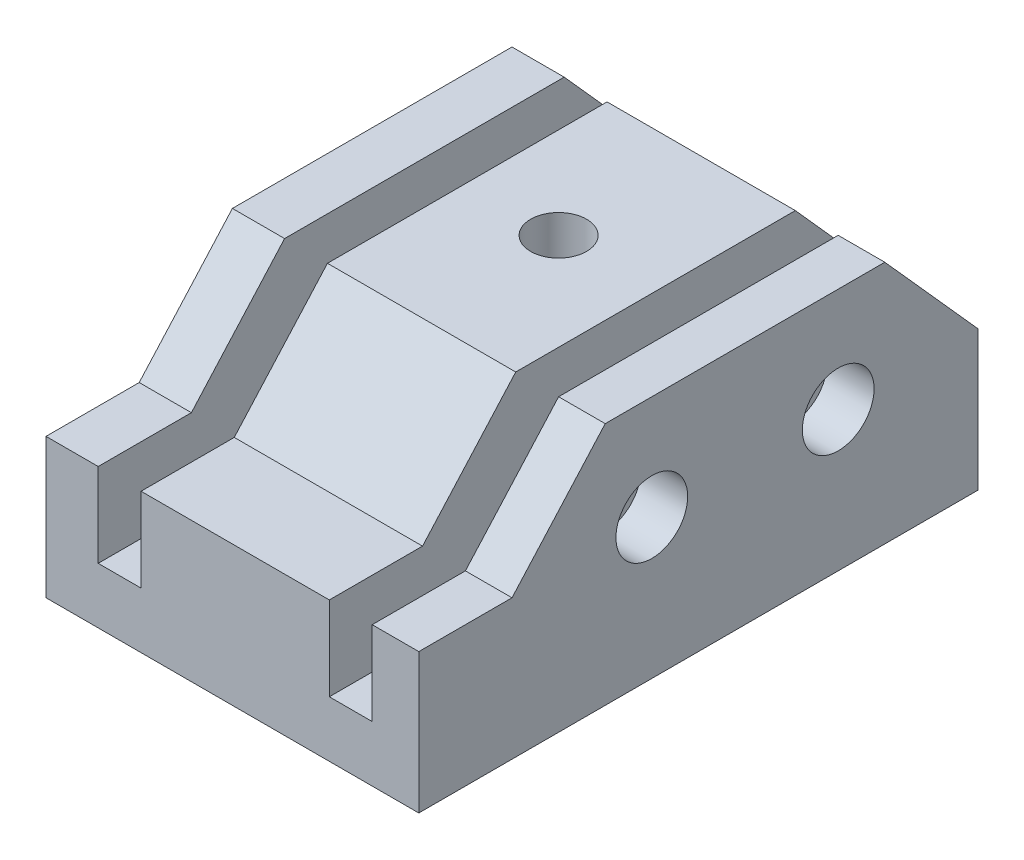
SolidWorks part; units mm, degrees
ref_plane "Front Plane" through (0, 0, 0) normal (0, 0, 1) x (1, 0, 0)
ref_plane "Top Plane" through (0, 0, 0) normal (0, 1, 0) x (1, 0, 0)
ref_plane "Right Plane" through (0, 0, 0) normal (1, 0, 0) x (0, 0, -1)
sketch "Sketch1" plane through (0, 0, 0) normal (1, 0, 0) x (0, 0, -1)
  line L1 (0, 0) -> (63.5, 0)
  line L2 (0, 0) -> (0, 6.35)
  line L3 (0, 6.35) -> (63.5, 6.35)
  line L4 (63.5, 0) -> (63.5, 6.35)
  dimension "D1" = 6.35
  dimension "D2" = 63.5
extrude "Boss-Extrude1" add sketch "Sketch1" against normal blind 50.8
sketch "Sketch2" plane through (0, 0, 0) normal (1, 0, 0) x (0, 0, -1)
  line L0 (0, 6.35) -> (0, 19.05)
  line L1 (0, 19.05) -> (12.7, 33.249)
  line L2 (12.7, 33.249) -> (50.8, 33.249)
  line L3 (50.8, 33.249) -> (63.5, 19.05)
  line L4 (63.5, 19.05) -> (63.5, 6.35)
  line L5 (63.5, 6.35) -> (0, 6.35)
  point P7 (31.75, 33.249)
  point P10 (31.75, 6.35)
  dimension "D1" = 38.1
  dimension "D2" = 12.7
  dimension "D3" = 12.7
  dimension "D4" = 19.05
  dimension "D5" = 19.05
extrude "Boss-Extrude2" add sketch "Sketch2" against normal blind 50.8
sketch "Sketch10" plane through (0, 0, -63.5) normal (0, 0, -1) x (-1, 0, 0)
  line L1 (50.8, 33.249) -> (0, 33.249) construction
  line L3 (6.35, 7.62) -> (6.35, 33.249)
  line L4 (6.35, 33.249) -> (12.192, 33.249)
  line L5 (12.192, 7.62) -> (12.192, 33.249)
  line L6 (6.35, 7.62) -> (12.192, 7.62)
  line L8 (50.8, 0) -> (0, 0) construction
  point P11 (12.192, 7.62)
  dimension "D1" = 7.62
  dimension "D2" = 5.842
  dimension "D3" = 6.35
extrude "Cut-Extrude1" cut sketch "Sketch10" against normal through all
pattern_linear "LPattern3" count 2 spacing 31.496 along (-1, 0, 0) of "Cut-Extrude1"
sketch "Sketch11" plane through (0, 0, 0) normal (1, 0, 0) x (0, 0, -1)
  circle A0 centre (19.05, 19.05) radius 4.8895
  circle A1 centre (19.05, 19.05) radius 7.9375 construction
  circle A2 centre (44.45, 19.05) radius 4.8895
  circle A3 centre (44.45, 19.05) radius 7.9375 construction
  dimension "D1" = 9.779
  dimension "D3" = 15.875
  dimension "D4" = 9.779
  dimension "D6" = 15.875
  dimension "D2" = 6.35
  dimension "D5" = 6.35
extrude "Cut-Extrude2" cut sketch "Sketch11" against normal through all
sketch "Sketch14" plane through (0, 33.249, 0) normal (0, 1, 0) x (1, 0, 0)
  line L3 (-37.846, 12.7) -> (-37.846, 50.8) construction
  point P0 (-25.4, 31.75)
  point P4 (-37.846, 31.75)
  dimension "D1" = 12.446
sketch "Sketch17" plane through (0, 40.0201, -44.7438) normal (0, 0.6667, -0.7454) x (-1, 0, 0)
  line L0 (12.192, -28.1343) -> (12.192, -9.0843) construction
  line L1 (37.846, -9.0843) -> (12.192, -9.0843) construction
  point P0 (25.019, -18.6093)
  point P4 (12.192, -18.6093)
  point P7 (25.019, -9.0843)
sketch "Sketch18" plane through (0, 8.4667, 9.466) normal (0, 0.6667, 0.7454) x (1, 0, 0)
  line L0 (-12.192, 33.249) -> (-12.192, 14.199) construction
  line L1 (-37.846, 33.249) -> (-12.192, 33.249) construction
  point P0 (-25.019, 23.724)
  point P1 (-25.019, 23.724)
  point P4 (-12.192, 23.724)
  point P7 (-25.019, 33.249)
ref_plane "Plane2" through (0, 33.02, 0) normal (0, -1, 0) x (-1, 0, 0)
fillet "Fillet1" [suppressed] radius 2.54
sketch "Sketch22" plane through (0, 0, 0) normal (0, 0, 1) x (1, 0, 0)
  line L0 (-50.8, 19.05) -> (-50.8, 0) construction
  line L1 (0, 0) -> (-50.8, 0)
  line L2 (0, 0) -> (0, 7.62)
  line L3 (-6.35, 7.62) -> (-12.192, 7.62)
  line L4 (-50.8, 0) -> (-50.8, 7.62)
  line L5 (-37.846, 7.62) -> (-37.846, 19.05)
  line L6 (-37.846, 19.05) -> (-12.192, 19.05)
  line L7 (-12.192, 19.05) -> (-12.192, 7.62)
  line L8 (-37.846, 7.62) -> (-43.688, 7.62)
  line L9 (-50.8, 7.62) -> (-50.8, 19.05)
  line L10 (-50.8, 19.05) -> (-43.688, 19.05)
  line L11 (-43.688, 19.05) -> (-43.688, 7.62)
  line L12 (-6.35, 7.62) -> (-6.35, 19.05)
  line L13 (-6.35, 19.05) -> (0, 19.05)
  line L14 (0, 19.05) -> (0, 7.62)
extrude "Boss-Extrude3" add sketch "Sketch22" along normal blind 12.7
sketch "Sketch23" plane through (0, 33.249, 0) normal (0, 1, 0) x (1, 0, 0)
  line L0 (-25.4, 63.5) -> (-25.4, -12.7) construction
  line L1 (-50.8, 63.5) -> (0, 63.5) construction
  line L2 (-50.8, -12.7) -> (0, -12.7) construction
  circle A0 centre (-25.4, 31.75) radius 3.81
  point P15 (-34.579, 50.8)
  dimension "D1" = 7.62
extrude "Cut-Extrude6" cut sketch "Sketch23" against normal through all
sketch "Sketch24" plane through (0, 0, 0) normal (0, -1, 0) x (1, 0, 0)
  line L0 (-25.4, -63.5) -> (-25.4, 12.7) construction
  line L1 (-13.97, -50.8) -> (-36.83, -50.8)
  line L2 (-13.97, -50.8) -> (-13.97, 7.62)
  line L3 (-13.97, 7.62) -> (-36.83, 7.62)
  line L4 (-36.83, -50.8) -> (-36.83, 7.62)
  line L5 (-50.8, -63.5) -> (0, -63.5) construction
  line L6 (-50.8, 12.7) -> (0, 12.7) construction
  line L7 (-25.4, -50.8) -> (-25.4, 7.62) construction
  circle A0 centre (-25.4, -31.75) radius 3.81 construction
  dimension "D1" = 58.42
  dimension "D2" = 19.05
  dimension "D3" = 22.86
extrude "Cut-Extrude7" cut sketch "Sketch24" against normal blind 4.58
sketch "Sketch25" plane through (0, 4.58, 0) normal (0, -1, 0) x (1, 0, 0)
  circle A0 centre (-25.4, -31.75) radius 7
  dimension "D1" = 14
extrude "Cut-Extrude8" cut sketch "Sketch25" against normal blind 2.8
sketch "Sketch26" plane through (0, 4.58, 0) normal (0, -1, 0) x (-1, 0, 0)
  line L0 (25.4, 50.8) -> (25.4, -7.62) construction
  line L1 (36.83, 50.8) -> (13.97, 50.8) construction
  line L2 (13.97, -7.62) -> (36.83, -7.62) construction
  circle A0 centre (30.4, 46.15) radius 3
  circle A1 centre (20.4, 46.15) radius 3
  circle A2 centre (25.4, 31.75) radius 7 construction
  circle A3 centre (20.4, -1.897) radius 3
  circle A4 centre (30.4, -1.897) radius 3
  dimension "D2" = 6
  dimension "D5" = 5
  dimension "D1" = 14.4
  dimension "D3" = 10
  dimension "D4" = 10
extrude "Cut-Extrude9" cut sketch "Sketch26" against normal blind 10
